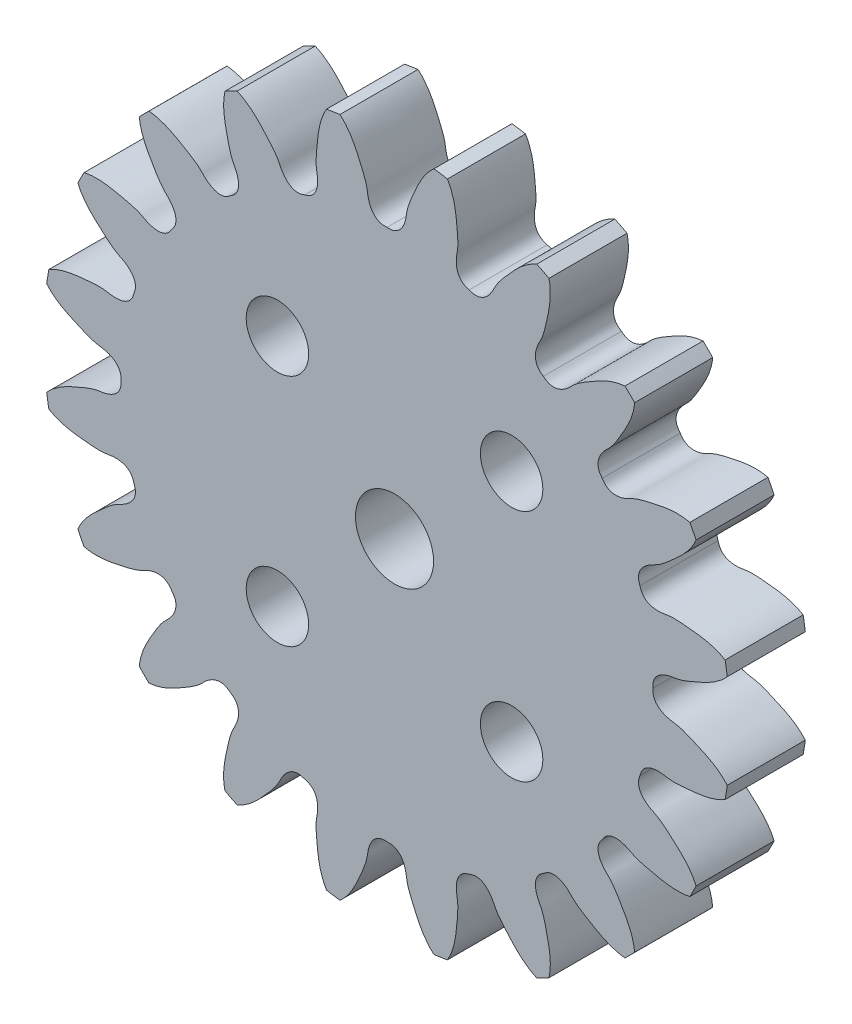
SolidWorks part; units mm, degrees
material "Plain Carbon Steel"
ref_plane "Front Plane" through (0, 0, 0) normal (0, 0, 1) x (1, 0, 0)
ref_plane "Top Plane" through (0, 0, 0) normal (0, 1, 0) x (1, 0, 0)
ref_plane "Right Plane" through (0, 0, 0) normal (1, 0, 0) x (0, 0, -1)
sketch "Sketch1" plane through (0, 0, 0) normal (0, 0, 1) x (1, 0, 0)
  circle A2 centre (-0.4838, 0) radius 22
  dimension "D3" = 44
extrude "Boss-Extrude1" add sketch "Sketch1" along normal blind 5
sketch "Sketch2" plane through (0, 0, 0) normal (0, 0, -1) x (-1, 0, 0)
  line L0 (-7.5, 7.5) -> (-7.5, -7.5) construction
  line L5 (-7.5, 7.5) -> (7.5, -7.5) construction
  line L6 (-7.5, -7.5) -> (6.0858, 6.0858) construction
  line L7 (-7.5, -7.5) -> (7.5, -7.5) construction
  line L8 (7.5, -7.5) -> (7.5, 7.5) construction
  line L9 (7.5, 7.5) -> (-7.5, 7.5) construction
  circle A0 centre (7.5, 7.5) radius 2
  circle A1 centre (7.5, -7.5) radius 2
  circle A2 centre (-7.5, -7.5) radius 2
  circle A3 centre (-7.5, 7.5) radius 2
  point P0 (0, 0)
  dimension "D3" = 4
  dimension "D4" = 4
  dimension "D5" = 4
  dimension "D6" = 4
  dimension "D1" = 15
  dimension "D2" = 15
extrude "Cut-Extrude1" cut sketch "Sketch2" against normal blind 30 contours A3 | A0 | A1 | A2
sketch "Sketch3" plane through (0, 0, 0) normal (0, 0, -1) x (-1, 0, 0)
  circle A0 centre (0, 0) radius 4
  dimension "D1" = 8
extrude "Boss-Extrude3" add sketch "Sketch3" along normal blind 9
sketch "Sketch4" plane through (0, 0, -9) normal (0, 0, -1) x (-1, 0, 0)
  circle A0 centre (0, 0) radius 2.5
  dimension "D1" = 5
extrude "Cut-Extrude2" cut sketch "Sketch4" against normal blind 16
sketch "Sketch6" plane through (0, 0, 0) normal (0, 0, -1) x (-1, 0, 0)
  line L0 (0.02, 0) -> (22.5102, 0) construction
  arc A0 (22.3194, -3.0589) -> (22.5102, 0) centre (0.4107, -0.1569) ccw
  arc A1 (22.3194, 3.0589) -> (22.5102, 0) centre (0.4107, 0.1569) cw
  spline S0 degree 3 poles (17.5209, 0) (17.5208, 0.0273) (17.522, 0.086) (17.5202, 0.1614) (17.5227, 0.2325) (17.5286, 0.2949) (17.5409, 0.3622) (17.5582, 0.4272) (17.5802, 0.4894) (17.6061, 0.5484) (17.6355, 0.604) (17.6678, 0.6562) (17.7025, 0.7049) (17.7392, 0.7504) (17.7777, 0.7929) (17.8176, 0.8324) (17.8589, 0.8694) (17.9013, 0.9038) (17.9448, 0.9361) (17.9892, 0.9662) (18.0347, 0.9945) (18.0812, 1.021) (18.1286, 1.0459) (18.177, 1.0692) (18.2264, 1.0911) (18.2769, 1.1116) (18.3284, 1.1308) (18.3809, 1.1487) (18.4345, 1.1654) (18.4893, 1.181) (18.5452, 1.1954) (18.6022, 1.2087) (18.6604, 1.2208) (18.7197, 1.2318) (18.7803, 1.2417) (18.842, 1.2507) (18.9812, 1.2663) (19.4058, 1.3478) (20.61, 1.8612) (21.7204, 2.3433) (22.3194, 3.0589) knots 0.490533 0.490533 0.490533 0.490533 0.49748 0.505459 0.509686 0.515561 0.521362 0.527065 0.532651 0.538108 0.543431 0.548622 0.553686 0.558635 0.563481 0.568238 0.572921 0.577544 0.582124 0.586672 0.591204 0.595731 0.600264 0.604813 0.609389 0.613999 0.618652 0.623354 0.628112 0.632931 0.637818 0.642776 0.64781 0.652923 0.65812 0.663404 0.668777 0.693733 0.772916 1 1 1 1
  spline S1 degree 3 poles (17.5209, 0) (17.5208, -0.0273) (17.522, -0.086) (17.5202, -0.1614) (17.5227, -0.2325) (17.5286, -0.2949) (17.5409, -0.3622) (17.5582, -0.4272) (17.5802, -0.4894) (17.6061, -0.5484) (17.6355, -0.604) (17.6678, -0.6562) (17.7025, -0.7049) (17.7392, -0.7504) (17.7777, -0.7929) (17.8176, -0.8324) (17.8589, -0.8694) (17.9013, -0.9038) (17.9448, -0.9361) (17.9892, -0.9662) (18.0347, -0.9945) (18.0812, -1.021) (18.1286, -1.0459) (18.177, -1.0692) (18.2264, -1.0911) (18.2769, -1.1116) (18.3284, -1.1308) (18.3809, -1.1487) (18.4345, -1.1654) (18.4893, -1.181) (18.5452, -1.1954) (18.6022, -1.2087) (18.6604, -1.2208) (18.7197, -1.2318) (18.7803, -1.2417) (18.842, -1.2507) (18.9812, -1.2663) (19.4058, -1.3478) (20.61, -1.8612) (21.7204, -2.3433) (22.3194, -3.0589) knots 0.490533 0.490533 0.490533 0.490533 0.49748 0.505459 0.509686 0.515561 0.521362 0.527065 0.532651 0.538108 0.543431 0.548622 0.553686 0.558635 0.563481 0.568238 0.572921 0.577544 0.582124 0.586672 0.591204 0.595731 0.600264 0.604813 0.609389 0.613999 0.618652 0.623354 0.628112 0.632931 0.637818 0.642776 0.64781 0.652923 0.65812 0.663404 0.668777 0.693733 0.772916 1 1 1 1
extrude "Cut-Extrude3" cut sketch "Sketch6" against normal blind 10
pattern_circular "CirPattern1" count 20 over 360 about axis through (-0.4838, 0, 0) along (0, 0, 1) of "Cut-Extrude3"
sketch "Sketch7" plane through (0, 0, 0) normal (0, 0, 1) x (1, 0, 0)
  circle A0 centre (0, 0) radius 20 construction
  circle A1 centre (0, 0) radius 18.7939 construction
  circle A2 centre (0, 0) radius 18.7991 construction
  circle A3 centre (0, 0) radius 22 construction
  circle A4 centre (0, 0) radius 17.1204 construction
  dimension "D1" = 40
  dimension "D2" = 37.5877
  dimension "D3" = 37.5983
  dimension "D4" = 44
  dimension "D5" = 34.2408
ref_axis "Axis1" through (0, 0, 28.149) along (0, 0, -1)
